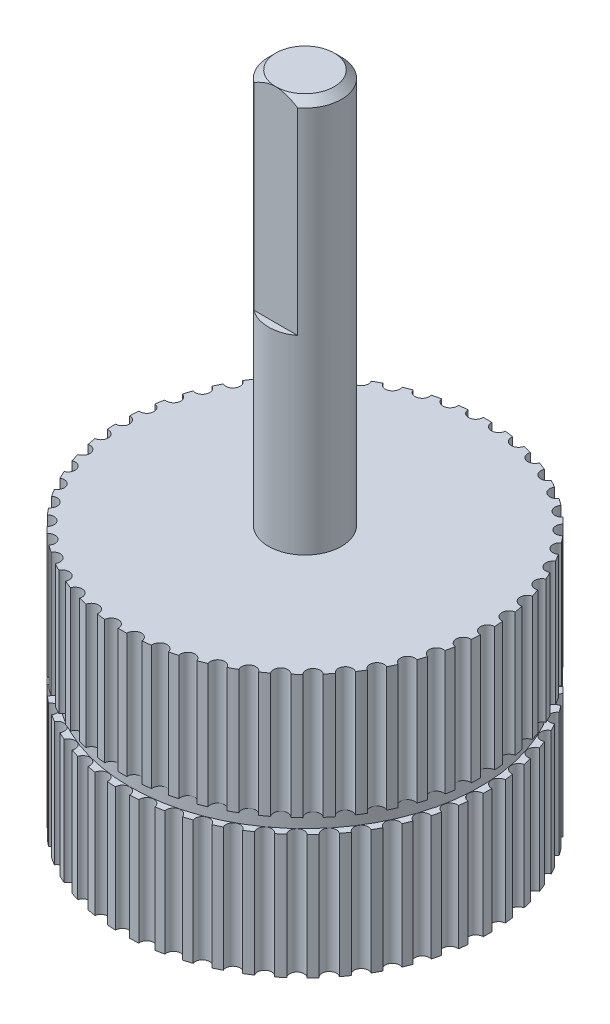
SolidWorks part; units mm, degrees
ref_plane "Front Plane" through (0, 0, 0) normal (0, 0, 1) x (1, 0, 0)
ref_plane "Top Plane" through (0, 0, 0) normal (0, 1, 0) x (1, 0, 0)
ref_plane "Right Plane" through (0, 0, 0) normal (1, 0, 0) x (0, 0, -1)
sketch "Sketch1" plane through (0, 0, 0) normal (0, 1, 0) x (1, 0, 0)
  circle A0 centre (0, 0) radius 2.5
  dimension "D1" = 5
extrude "Boss-Extrude1" add sketch "Sketch1" along normal blind 51
chamfer "Chamfer1" distance 0.5 angle 45 2 edges at (0, 0, 2.5) (0, 51, 2.5)
sketch "Sketch2" plane through (0, 51, 0) normal (0, 1, 0) x (1, 0, 0)
  line L0 (-1.5, -2) -> (1.5, -2)
  circle A0 centre (0, 0) radius 2.5 construction
  arc A1 (-1.5, -2) -> (1.5, -2) centre (0, 0) ccw
  dimension "D1" = 2
extrude "Cut-Extrude1" cut sketch "Sketch2" against normal blind 14
sketch "Sketch3" plane through (0, 0, 0) normal (0, -1, 0) x (1, 0, 0)
  line L3 (0.4907, 12.4904) -> (0, 0) construction
  line L4 (0, 0) -> (-0.4907, 12.4904) construction
  arc A0 (1.0786, 12.4534) -> (0.4907, 12.4904) centre (0, 0) ccw
  arc A1 (-0.4907, 12.4904) -> (0.4907, 12.4904) centre (0, 12.5) ccw
  arc A2 (1.0786, 12.4534) -> (2.0523, 12.3304) centre (1.5667, 12.4014) ccw
  arc A3 (2.6309, 12.22) -> (2.0523, 12.3304) centre (0, 0) ccw
  arc A4 (2.6309, 12.22) -> (3.5816, 11.9759) centre (3.1086, 12.1073) ccw
  arc A5 (4.1417, 11.7939) -> (3.5816, 11.9759) centre (0, 0) ccw
  arc A6 (4.1417, 11.7939) -> (5.0543, 11.4326) centre (4.6016, 11.6222) ccw
  arc A7 (5.5872, 11.1818) -> (5.0543, 11.4326) centre (0, 0) ccw
  arc A8 (5.5872, 11.1818) -> (6.4473, 10.709) centre (6.0219, 10.9538) ccw
  arc A9 (6.9446, 10.3934) -> (6.4473, 10.709) centre (0, 0) ccw
  arc A10 (6.9446, 10.3934) -> (7.7387, 9.8165) centre (7.3473, 10.1127) ccw
  arc A11 (8.1925, 9.441) -> (7.7387, 9.8165) centre (0, 0) ccw
  arc A12 (8.1925, 9.441) -> (8.908, 8.7691) centre (8.5568, 9.1121) ccw
  arc A13 (9.3112, 8.3398) -> (8.908, 8.7691) centre (0, 0) ccw
  arc A14 (9.3112, 8.3398) -> (9.9368, 7.5835) centre (9.6314, 7.9678) ccw
  arc A15 (10.283, 7.107) -> (9.9368, 7.5835) centre (0, 0) ccw
  arc A16 (10.283, 7.107) -> (10.8089, 6.2783) centre (10.5541, 6.6978) ccw
  arc A17 (11.0927, 5.7622) -> (10.8089, 6.2783) centre (0, 0) ccw
  arc A18 (11.0927, 5.7622) -> (11.5106, 4.8741) centre (11.3103, 5.3222) ccw
  arc A19 (11.7274, 4.3265) -> (11.5106, 4.8741) centre (0, 0) ccw
  arc A20 (11.7274, 4.3265) -> (12.0307, 3.393) centre (11.8882, 3.8627) ccw
  arc A21 (12.1772, 2.8225) -> (12.0307, 3.393) centre (0, 0) ccw
  arc A22 (12.1772, 2.8225) -> (12.3611, 1.8584) centre (12.2786, 2.3423) ccw
  arc A23 (12.4349, 1.2741) -> (12.3611, 1.8584) centre (0, 0) ccw
  arc A24 (12.4349, 1.2741) -> (12.4965, 0.2945) centre (12.4753, 0.7849) ccw
  arc A25 (12.4965, -0.2945) -> (12.4965, 0.2945) centre (0, 0) ccw
  arc A26 (12.4965, -0.2945) -> (12.4349, -1.2741) centre (12.4753, -0.7849) ccw
  arc A27 (12.3611, -1.8584) -> (12.4349, -1.2741) centre (0, 0) ccw
  arc A28 (12.3611, -1.8584) -> (12.1772, -2.8225) centre (12.2786, -2.3423) ccw
  arc A29 (12.0307, -3.393) -> (12.1772, -2.8225) centre (0, 0) ccw
  arc A30 (12.0307, -3.393) -> (11.7274, -4.3265) centre (11.8882, -3.8627) ccw
  arc A31 (11.5106, -4.8741) -> (11.7274, -4.3265) centre (0, 0) ccw
  arc A32 (11.5106, -4.8741) -> (11.0927, -5.7622) centre (11.3103, -5.3222) ccw
  arc A33 (10.8089, -6.2783) -> (11.0927, -5.7622) centre (0, 0) ccw
  arc A34 (10.8089, -6.2783) -> (10.283, -7.107) centre (10.5541, -6.6978) ccw
  arc A35 (9.9368, -7.5835) -> (10.283, -7.107) centre (0, 0) ccw
  arc A36 (9.9368, -7.5835) -> (9.3112, -8.3398) centre (9.6314, -7.9678) ccw
  arc A37 (8.908, -8.7691) -> (9.3112, -8.3398) centre (0, 0) ccw
  arc A38 (8.908, -8.7691) -> (8.1925, -9.441) centre (8.5568, -9.1121) ccw
  arc A39 (7.7387, -9.8165) -> (8.1925, -9.441) centre (0, 0) ccw
  arc A40 (7.7387, -9.8165) -> (6.9446, -10.3934) centre (7.3473, -10.1127) ccw
  arc A41 (6.4473, -10.709) -> (6.9446, -10.3934) centre (0, 0) ccw
  arc A42 (6.4473, -10.709) -> (5.5872, -11.1818) centre (6.0219, -10.9538) ccw
  arc A43 (5.0543, -11.4326) -> (5.5872, -11.1818) centre (0, 0) ccw
  arc A44 (5.0543, -11.4326) -> (4.1417, -11.7939) centre (4.6016, -11.6222) ccw
  arc A45 (3.5816, -11.9759) -> (4.1417, -11.7939) centre (0, 0) ccw
  arc A46 (3.5816, -11.9759) -> (2.6309, -12.22) centre (3.1086, -12.1073) ccw
  arc A47 (2.0523, -12.3304) -> (2.6309, -12.22) centre (0, 0) ccw
  arc A48 (2.0523, -12.3304) -> (1.0786, -12.4534) centre (1.5667, -12.4014) ccw
  arc A49 (0.4907, -12.4904) -> (1.0786, -12.4534) centre (0, 0) ccw
  arc A50 (0.4907, -12.4904) -> (-0.4907, -12.4904) centre (0, -12.5) ccw
  arc A51 (-1.0786, -12.4534) -> (-0.4907, -12.4904) centre (0, 0) ccw
  arc A52 (-1.0786, -12.4534) -> (-2.0523, -12.3304) centre (-1.5667, -12.4014) ccw
  arc A53 (-2.6309, -12.22) -> (-2.0523, -12.3304) centre (0, 0) ccw
  arc A54 (-2.6309, -12.22) -> (-3.5816, -11.9759) centre (-3.1086, -12.1073) ccw
  arc A55 (-4.1417, -11.7939) -> (-3.5816, -11.9759) centre (0, 0) ccw
  arc A56 (-4.1417, -11.7939) -> (-5.0543, -11.4326) centre (-4.6016, -11.6222) ccw
  arc A57 (-5.5872, -11.1818) -> (-5.0543, -11.4326) centre (0, 0) ccw
  arc A58 (-5.5872, -11.1818) -> (-6.4473, -10.709) centre (-6.0219, -10.9538) ccw
  arc A59 (-6.9446, -10.3934) -> (-6.4473, -10.709) centre (0, 0) ccw
  arc A60 (-6.9446, -10.3934) -> (-7.7387, -9.8165) centre (-7.3473, -10.1127) ccw
  arc A61 (-8.1925, -9.441) -> (-7.7387, -9.8165) centre (0, 0) ccw
  arc A62 (-8.1925, -9.441) -> (-8.908, -8.7691) centre (-8.5568, -9.1121) ccw
  arc A63 (-9.3112, -8.3398) -> (-8.908, -8.7691) centre (0, 0) ccw
  arc A64 (-9.3112, -8.3398) -> (-9.9368, -7.5835) centre (-9.6314, -7.9678) ccw
  arc A65 (-10.283, -7.107) -> (-9.9368, -7.5835) centre (0, 0) ccw
  arc A66 (-10.283, -7.107) -> (-10.8089, -6.2783) centre (-10.5541, -6.6978) ccw
  arc A67 (-11.0927, -5.7622) -> (-10.8089, -6.2783) centre (0, 0) ccw
  arc A68 (-11.0927, -5.7622) -> (-11.5106, -4.8741) centre (-11.3103, -5.3222) ccw
  arc A69 (-11.7274, -4.3265) -> (-11.5106, -4.8741) centre (0, 0) ccw
  arc A70 (-11.7274, -4.3265) -> (-12.0307, -3.393) centre (-11.8882, -3.8627) ccw
  arc A71 (-12.1772, -2.8225) -> (-12.0307, -3.393) centre (0, 0) ccw
  arc A72 (-12.1772, -2.8225) -> (-12.3611, -1.8584) centre (-12.2786, -2.3423) ccw
  arc A73 (-12.4349, -1.2741) -> (-12.3611, -1.8584) centre (0, 0) ccw
  arc A74 (-12.4349, -1.2741) -> (-12.4965, -0.2945) centre (-12.4753, -0.7849) ccw
  arc A75 (-12.4965, 0.2945) -> (-12.4965, -0.2945) centre (0, 0) ccw
  arc A76 (-12.4965, 0.2945) -> (-12.4349, 1.2741) centre (-12.4753, 0.7849) ccw
  arc A77 (-12.3611, 1.8584) -> (-12.4349, 1.2741) centre (0, 0) ccw
  arc A78 (-12.3611, 1.8584) -> (-12.1772, 2.8225) centre (-12.2786, 2.3423) ccw
  arc A79 (-12.0307, 3.393) -> (-12.1772, 2.8225) centre (0, 0) ccw
  arc A80 (-12.0307, 3.393) -> (-11.7274, 4.3265) centre (-11.8882, 3.8627) ccw
  arc A81 (-11.5106, 4.8741) -> (-11.7274, 4.3265) centre (0, 0) ccw
  arc A82 (-11.5106, 4.8741) -> (-11.0927, 5.7622) centre (-11.3103, 5.3222) ccw
  arc A83 (-10.8089, 6.2783) -> (-11.0927, 5.7622) centre (0, 0) ccw
  arc A84 (-10.8089, 6.2783) -> (-10.283, 7.107) centre (-10.5541, 6.6978) ccw
  arc A85 (-9.9368, 7.5835) -> (-10.283, 7.107) centre (0, 0) ccw
  arc A86 (-9.9368, 7.5835) -> (-9.3112, 8.3398) centre (-9.6314, 7.9678) ccw
  arc A87 (-8.908, 8.7691) -> (-9.3112, 8.3398) centre (0, 0) ccw
  arc A88 (-8.908, 8.7691) -> (-8.1925, 9.441) centre (-8.5568, 9.1121) ccw
  arc A89 (-7.7387, 9.8165) -> (-8.1925, 9.441) centre (0, 0) ccw
  arc A90 (-7.7387, 9.8165) -> (-6.9446, 10.3934) centre (-7.3473, 10.1127) ccw
  arc A91 (-6.4473, 10.709) -> (-6.9446, 10.3934) centre (0, 0) ccw
  arc A92 (-6.4473, 10.709) -> (-5.5872, 11.1818) centre (-6.0219, 10.9538) ccw
  arc A93 (-5.0543, 11.4326) -> (-5.5872, 11.1818) centre (0, 0) ccw
  arc A94 (-5.0543, 11.4326) -> (-4.1417, 11.7939) centre (-4.6016, 11.6222) ccw
  arc A95 (-3.5816, 11.9759) -> (-4.1417, 11.7939) centre (0, 0) ccw
  arc A96 (-3.5816, 11.9759) -> (-2.6309, 12.22) centre (-3.1086, 12.1073) ccw
  arc A97 (-2.0523, 12.3304) -> (-2.6309, 12.22) centre (0, 0) ccw
  arc A98 (-2.0523, 12.3304) -> (-1.0786, 12.4534) centre (-1.5667, 12.4014) ccw
  arc A99 (-0.4907, 12.4904) -> (-1.0786, 12.4534) centre (0, 0) ccw
  point P1 (1.1644, 13.0561)
  point P6 (-0.5452, 12.5)
  point P8 (1.0242, 12.458)
  point P11 (-0.5452, 12.5)
  point P13 (-1.0242, 12.458)
  point P14 (0.8361, 12.4966)
  point P17 (0, 0)
  dimension "D1" = 12.5
  dimension "D3" = 50
  dimension "D4" = 4.5
extrude "Boss-Extrude2" add sketch "Sketch3" against normal blind 8.5 from offset 6 offset against normal yes
sketch "Sketch4" plane through (0, 14.5, 0) normal (0, 1, 0) x (1, 0, 0)
  circle A0 centre (0, 0) radius 12
  dimension "D1" = 24
extrude "Boss-Extrude3" add sketch "Sketch4" along normal blind 1
extrude "Boss-Extrude4" add sketch "Sketch3<2>" against normal blind 8.5 from offset 15.5 separate body offset against normal yes
sketch "Sketch3<2>" plane through (0, 0, 0) normal (0, -1, 0) x (1, 0, 0) same geometry as "Sketch3"
move or copy body "Body-Move/Copy1" bodies to move or copy 105 copy no rotation origin (0, 0, 0) rotation axis (0, 1, 0) rotation angle 3.6
combine bodies "Combine1" operation type add bodies to combine 104 106
